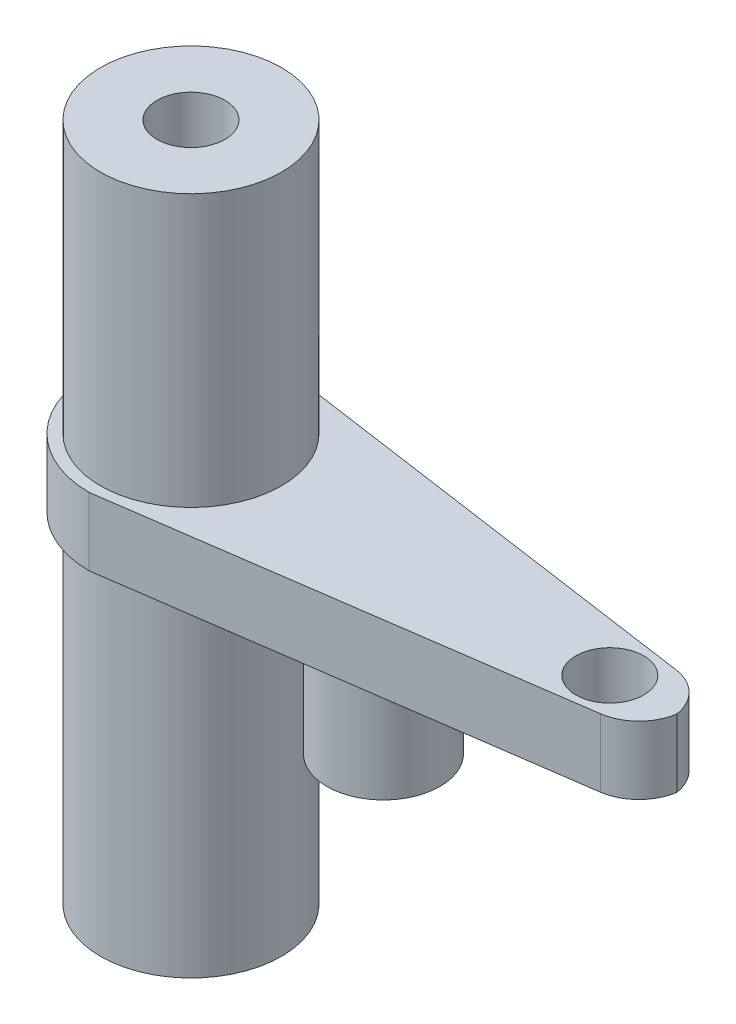
SolidWorks part; units mm, degrees
material "PBT General Purpose"
ref_plane "Front Plane" through (0, 0, 0) normal (0, 0, 1) x (1, 0, 0)
ref_plane "Top Plane" through (0, 0, 0) normal (0, 1, 0) x (1, 0, 0)
ref_plane "Right Plane" through (0, 0, 0) normal (1, 0, 0) x (0, 0, -1)
sketch "Sketch1" plane through (0, 0, 0) normal (0, 1, 0) x (1, 0, 0)
  circle A0 centre (0, 0) radius 4
  dimension "D1" = 8
extrude "Boss-Extrude1" add sketch "Sketch1" along normal blind 15
sketch "Sketch2" plane through (0, 15, 0) normal (0, 1, 0) x (1, 0, 0)
  line L0 (0, 0) -> (17, 0) construction
  line L1 (0, 4.5) -> (17, 4.5)
  line L2 (0, -4.5) -> (17, -4.5)
  line L3 (0, 4.5) -> (21.2566, 1.4598)
  line L4 (0, -4.5) -> (21.2566, -1.4598)
  arc A0 (0, 4.5) -> (0, -4.5) centre (0, 0) ccw
  arc A1 (17, -4.5) -> (17, 4.5) centre (17, 0) ccw
  circle A2 centre (18.5, 0) radius 1.5
  point P3 (8.5, 0)
  point P10 (21.5, 0)
  dimension "D2" = 4.5
  dimension "D4" = 3
  dimension "D1" = 17
  dimension "D3" = 3
extrude "Boss-Extrude4" add sketch "Sketch2" along normal blind 3
fillet "Fillet4" radius 2 2 edges at (21.2566, 16.5, -1.4598) (21.2566, 16.5, 1.4598)
sketch "Sketch7" plane through (0, 18, 0) normal (0, 1, 0) x (1, 0, 0)
  circle A0 centre (0, 0) radius 4
  dimension "D1" = 8
extrude "Boss-Extrude5" add sketch "Sketch7" along normal blind 13
sketch "Sketch8" plane through (0, 31, 0) normal (0, 1, 0) x (1, 0, 0)
  circle A0 centre (0, 0) radius 1.5
  circle A1 centre (0, 0) radius 4 construction
  dimension "D1" = 2.5
extrude "Cut-Extrude6" cut sketch "Sketch8" against normal blind 10
cosmetic thread "Cosmetic Thread5" parameters "D1"=4, "D2"=4
sketch "Sketch10" plane through (0, 0, 0) normal (0, -1, 0) x (1, 0, 0)
  circle A0 centre (0, 0) radius 1.25
  dimension "D1" = 2.5
extrude "Cut-Extrude7" cut sketch "Sketch10" against normal blind 10
cosmetic thread "Cosmetic Thread4" parameters "D1"=5, "D2"=3
sketch "Sketch11" plane through (0, 15, 0) normal (0, -1, 0) x (1, 0, 0)
  circle A0 centre (8.5, 0) radius 2.5
  dimension "D2" = 5
  dimension "D1" = 8.5
extrude "Boss-Extrude6" add sketch "Sketch11" along normal blind 5
sketch "Sketch12" plane through (0, 10, 0) normal (0, -1, 0) x (1, 0, 0)
  circle A0 centre (8.5, 0) radius 1.25
  dimension "D1" = 2.5
extrude "Cut-Extrude8" cut sketch "Sketch12" against normal blind 5
cosmetic thread "Cosmetic Thread6" parameters "D1"=5, "D2"=3
sketch "Sketch14" plane through (0, 31, 0) normal (0, 1, 0) x (1, 0, 0)
  circle A0 centre (0, 0) radius 4
extrude "Cut-Extrude10" cut sketch "Sketch14" against normal blind 1
